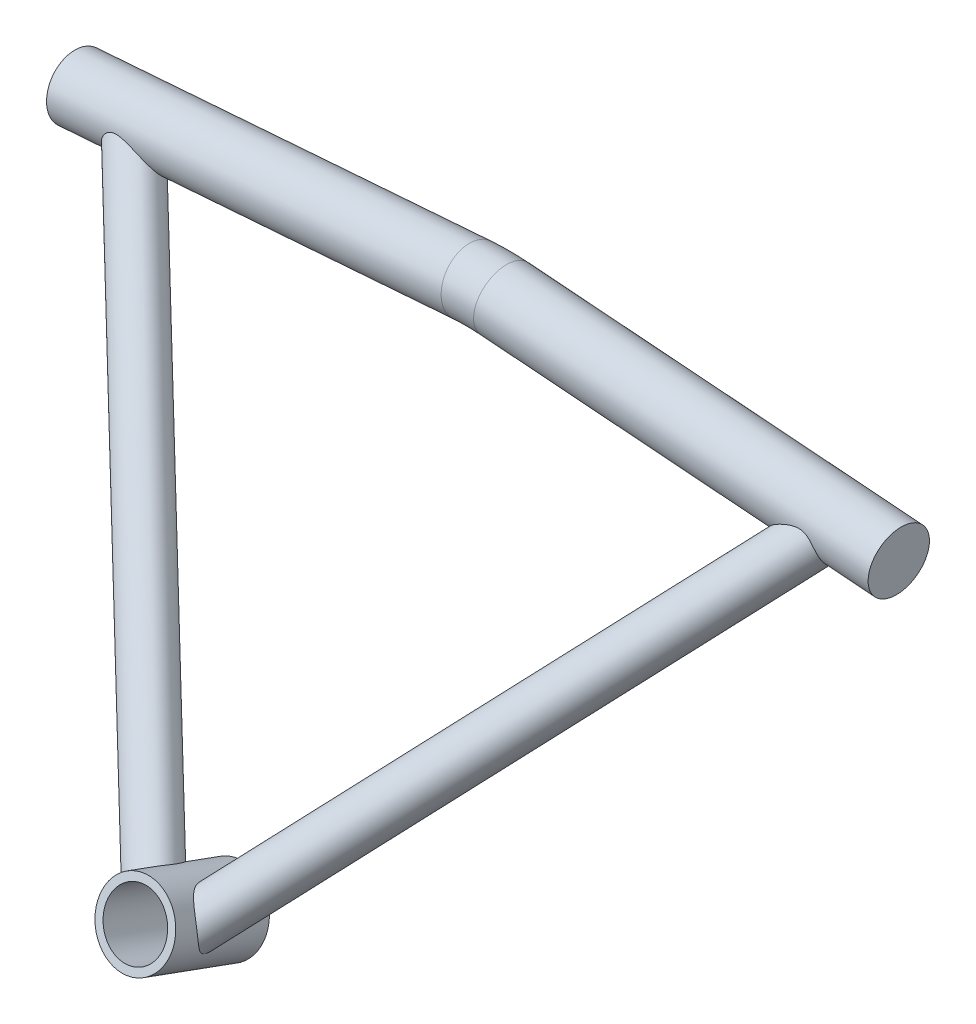
SolidWorks part; units mm, degrees
material "AISI 4130 Steel, normalized at 870C"
ref_plane "Front Plane" through (0, 0, 0) normal (0, 0, 1) x (1, 0, 0)
ref_plane "Top Plane" through (0, 0, 0) normal (0, 1, 0) x (1, 0, 0)
ref_plane "Right Plane" through (0, 0, 0) normal (1, 0, 0) x (0, 0, -1)
sketch "Sketch3" plane through (0, 0, 0) normal (0, 1, 0) x (1, 0, 0)
  line L0 (-5.08, -6.35) -> (5.08, -6.35) construction
  line L2 (0, -88.2205) -> (0, 88.2205) construction
  line L3 (5.08, 0) -> (-5.08, 0) construction
  dimension "D1" = 5.08
  dimension "D2" = 10.16
  dimension "D3" = 6.35
  dimension "D4" = 10.16
  dimension "D5" = 5.08
ref_plane "Plane1" through (0, 3.1441, 3.6169) normal (0, 0.6561, 0.7547) x (1, 0, 0)
ref_plane "Plane3" through (0, 0, 0) normal (0, 0.342, 0.9397) x (-1, 0, 0)
sketch "Sketch1" plane through (0, 0, 0) normal (0, 0.342, 0.9397) x (1, 0, 0)
  circle A0 centre (0, 0) radius 15.875
  dimension "D1" = 31.75
extrude "Boss-Extrude1" add sketch "Sketch1" along normal mid plane 41.402 contours A0
sketch "Sketch4" plane through (0, 3.1441, 3.6169) normal (0, 0.6561, 0.7547) x (1, 0, 0)
  line L0 (-5.08, -4.166) -> (-143.484, 193.4954)
  line L2 (0, -99.0717) -> (0, 99.0717) construction
  dimension "D2" = 35
  dimension "D3" = 241.3
sweep "Sweep1" add path "Sketch4" circular profile diameter 19.05 parameters "D3"=19.05
sketch "Sketch15" plane through (0, 3.1441, 3.6169) normal (0, 0.6561, 0.7547) x (1, 0, 0)
  line L0 (5.08, -4.166) -> (143.484, 193.4954)
  line L1 (0, -99.0717) -> (0, 99.0717) construction
  dimension "D1" = 241.3
  dimension "D2" = 35
sweep "Sweep2" add path "Sketch15" circular profile diameter 19.05 parameters "D3"=19.05
sketch "Sketch36" plane through (-138.1179, 148.8686, -129.4095) normal (-0.5736, 0.6182, -0.5374) x (0.8191, 0.4394, -0.3687)
  circle A0 centre (-6.5024, -4.8578) radius 7.9375
  dimension "D1" = 15.875
extrude "Cut-Extrude2" cut sketch "Sketch36" against normal up to surface (251.5099 mm away) up to face at (15.2328, -2.8486, 5.2417)
sketch "Sketch37" plane through (138.1179, 148.8686, -129.4095) normal (0.5736, 0.6182, -0.5374) x (0.8191, -0.4394, 0.3687)
  circle A0 centre (6.5024, -4.8578) radius 7.9375
  dimension "D1" = 15.875
extrude "Cut-Extrude3" cut sketch "Sketch37" against normal up to surface (226.8376 mm away) up to face at (10.6472, -5.7729, 18.5671)
sketch "Sketch77" plane through (0, 7.0802, 19.4526) normal (0, 0.342, 0.9397) x (1, 0, 0)
  circle A1 centre (0, 0) radius 15.875
extrude "Boss-Extrude2" add sketch "Sketch77" against normal up to surface (41.402 mm away) up to face at (0, -21.9978, -14.023)
sketch "Sketch2" plane through (0, -7.0802, -19.4526) normal (0, -0.342, -0.9397) x (-1, 0, 0)
  circle A0 centre (0, 0) radius 12.7
  dimension "D1" = 25.4
extrude "Cut-Extrude1" cut sketch "Sketch2" against normal up to next
ref_plane "Plane2" through (0, 0, -127) normal (0, 0, 1) x (1, 0, 0)
sketch "Sketch40" plane through (-106.934, 0, -127) normal (0, 0, 1) x (1, 0, 0)
  line L2 (106.934, -85.9333) -> (106.934, 85.9333) construction
  line L3 (100.2024, 162.3048) -> (-63.6638, 149.8608)
  line L4 (113.6656, 162.3048) -> (277.5318, 149.8608)
  arc A0 (100.2024, 162.3048) -> (113.6656, 162.3048) centre (106.934, 73.66) cw
  point P0 (106.934, 162.56)
  point P7 (106.934, 162.56)
  dimension "D1" = 164.338
  dimension "D3" = 88.9
  dimension "D2" = 164.338
  dimension "D4" = 4.75
sweep "Sweep3" add path "Sketch40" circular profile diameter 25.4 parameters "D3"=25.4
